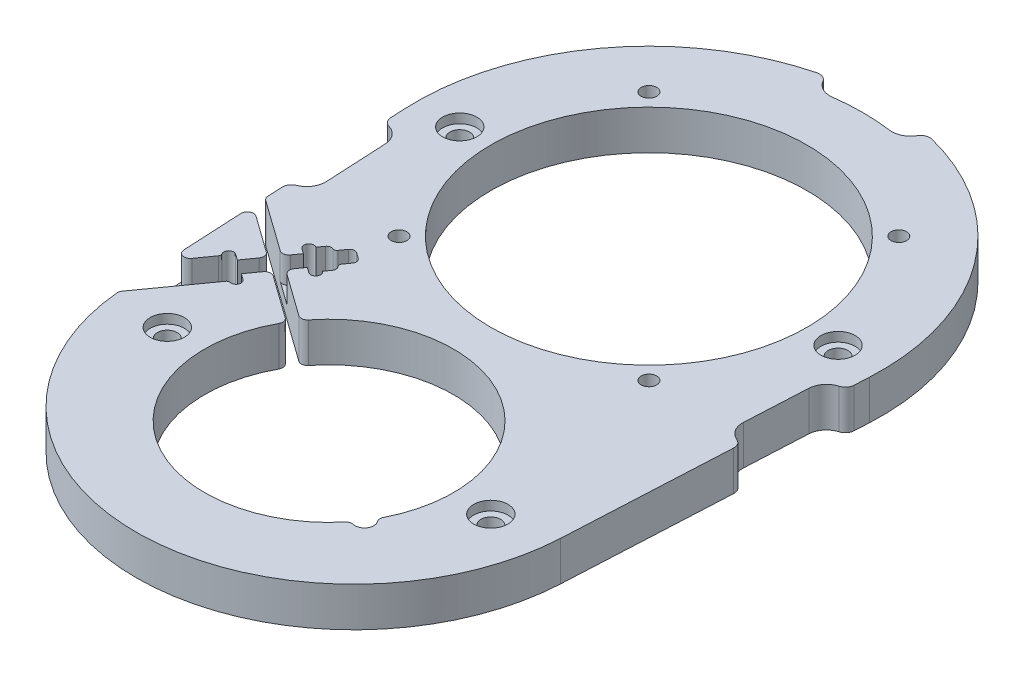
SolidWorks part; units mm, degrees
material "PC High Viscosity"
ref_plane "Front Plane" through (0, 0, 0) normal (0, 0, 1) x (1, 0, 0)
ref_plane "Top Plane" through (0, 0, 0) normal (0, 1, 0) x (1, 0, 0)
ref_plane "Right Plane" through (0, 0, 0) normal (1, 0, 0) x (0, 0, -1)
sketch "Sketch1" plane through (0, 0, 0) normal (0, 1, 0) x (1, 0, 0)
  line L0 (0, 0) -> (0, 102.8) construction
  line L1 (0, 0) -> (0, -40) construction
  line L2 (0, -40) -> (0, -52) construction
  line L3 (-74.7041, 99.0127) -> (-69.9102, 4.4557)
  line L4 (74.7041, 99.0127) -> (69.9102, 4.4557)
  line L5 (0, 102.8) -> (0, 165.6) construction
  line L6 (0, 102.8) -> (44.4063, 147.2063) construction
  line L7 (0, 102.8) -> (62.8, 102.8) construction
  line L8 (35.921, 138.721) -> (44.4063, 147.2063) construction
  line L10 (0, 102.8) -> (-74.8, 102.8) construction
  line L11 (0, 102.8) -> (0, 177.6) construction
  line L12 (0, 177.6) -> (-74.8, 177.6) construction
  line L13 (-74.8, 102.8) -> (-74.8, 177.6) construction
  line L14 (0, 0) -> (-74.8, 0) construction
  line L15 (0, 0) -> (0, -62) construction
  line L16 (0, -62) -> (-74.8, -62) construction
  line L17 (-74.8, 0) -> (-74.8, -62) construction
  circle A0 centre (0, 0) radius 40
  circle A1 centre (0, 102.8) radius 50.8
  circle A2 centre (0, 102.8) radius 62.8 construction
  circle A3 centre (0, 102.8) radius 74.8 construction
  circle A4 centre (0, 8) radius 60 construction
  circle A5 centre (0, 8) radius 70 construction
  arc A6 (-74.7041, 99.0127) -> (74.7041, 99.0127) centre (0, 102.8) cw
  arc A7 (-69.9102, 4.4557) -> (69.9102, 4.4557) centre (0, 8) ccw
  circle A8 centre (40.1637, 142.9637) radius 2.5
  circle A9 centre (40.1637, 62.6363) radius 2.5
  circle A10 centre (-40.1637, 62.6363) radius 2.5
  circle A11 centre (-40.1637, 142.9637) radius 2.5
  circle A12 centre (0, 102.8) radius 56.8 construction
  point P32 (0, 102.8)
  dimension "D1" = 80
  dimension "D2" = 101.6
  dimension "D4" = 12
  dimension "D3" = 12
  dimension "D5" = 10
  dimension "D6" = 120
  dimension "D7" = 12
  dimension "D9" = 5
  dimension "D8" = 45
  dimension "D11" = 239.6
  dimension "D12" = 149.6
  dimension "D10" = 4
extrude "Boss-Extrude1" add sketch "Sketch1" along normal blind 12.7
sketch "Sketch2" plane through (0, 0, 0) normal (0, -1, 0) x (1, 0, 0)
  line L0 (67.713, -99.3671) -> (62.9192, -4.8101)
  line L1 (-62.9192, -4.8101) -> (-67.713, -99.3671)
  line L2 (74.7041, -99.0127) -> (69.9102, -4.4557)
  line L3 (-69.9102, -4.4557) -> (-74.7041, -99.0127)
  line L4 (74.7041, -99.0127) -> (69.9102, -4.4557) construction
  line L5 (-69.9102, -4.4557) -> (-74.7041, -99.0127) construction
  line L6 (-57.1766, -5.1013) -> (-61.9704, -99.6582)
  line L7 (61.9704, -99.6582) -> (57.1766, -5.1013)
  arc A0 (62.9192, -4.8101) -> (-62.9192, -4.8101) centre (0, -8) ccw
  arc A1 (-67.713, -99.3671) -> (67.713, -99.3671) centre (0, -102.8) ccw
  arc A2 (-74.7041, -99.0127) -> (74.7041, -99.0127) centre (0, -102.8) ccw
  arc A3 (69.9102, -4.4557) -> (-69.9102, -4.4557) centre (0, -8) ccw
  arc A4 (-74.7041, -99.0127) -> (74.7041, -99.0127) centre (0, -102.8) ccw construction
  arc A5 (69.9102, -4.4557) -> (-69.9102, -4.4557) centre (0, -8) ccw construction
  arc A6 (57.1766, -5.1013) -> (-57.1766, -5.1013) centre (0, -8) ccw
  arc A7 (-61.9704, -99.6582) -> (61.9704, -99.6582) centre (0, -102.8) ccw
  dimension "D1" = 0
  dimension "D2" = 7
  dimension "D3" = 5.75
sketch "Sketch3" plane through (0, 12.7, 0) normal (0, 1, 0) x (1, 0, 0)
  line L0 (0, 0) -> (-72.3071, 51.7342)
  line L1 (-74.7041, 99.0127) -> (-69.9102, 4.4557) construction
  line L2 (0, 0) -> (0, 177.6) construction
  line L3 (-1.862, -2.6025) -> (-74.1692, 49.1317)
  line L4 (0, 0) -> (-1.862, -2.6025)
  line L5 (-72.3071, 51.7342) -> (-74.1692, 49.1317)
  arc A0 (74.7041, 99.0127) -> (-74.7041, 99.0127) centre (0, 102.8) ccw construction
  point P5 (-72.3071, 51.7342)
  dimension "D1" = 3.2
extrude "Cut-Extrude1" cut sketch "Sketch3" against normal through all
sketch "Sketch4" plane through (0, 12.7, 0) normal (0, 1, 0) x (1, 0, 0)
  line L0 (-53.1944, 34.1247) -> (-70.2088, 10.3444) construction
  line L1 (-72.1001, 47.6514) -> (-34.2887, 20.5981) construction
  line L2 (-72.1001, 47.6514) -> (-69.9102, 4.4557) construction
  line L3 (-55.4309, 35.7249) -> (-72.4453, 11.9446)
  line L4 (-50.9579, 32.5246) -> (-69.985, 5.9311)
  line L5 (-50.9579, 32.5246) -> (-67.9723, 8.7442) construction
  line L6 (-72.4453, 11.9446) -> (-69.985, 5.9311)
  line L7 (-55.4309, 35.7249) -> (-50.9579, 32.5246)
  dimension "D1" = 2.75
  dimension "D2" = 2.75
extrude "Cut-Extrude2" cut sketch "Sketch4" against normal blind 8.5
sketch "Sketch5" plane through (0, 12.7, 0) normal (0, 1, 0) x (1, 0, 0)
  line L0 (-55.4309, 35.7249) -> (-50.9579, 32.5246) construction
  line L1 (-53.1944, 34.1247) -> (-41.4405, 50.5529) construction
  line L2 (-32.531, 23.2752) -> (-72.3071, 51.7342) construction
  line L3 (-50.9579, 32.5246) -> (-39.204, 48.9527)
  line L4 (-55.4309, 35.7249) -> (-43.677, 52.1531)
  line L5 (-43.677, 52.1531) -> (-39.204, 48.9527)
  line L6 (-50.9579, 32.5246) -> (-55.4309, 35.7249)
  dimension "D1" = 17
  dimension "D2" = 2.75
  dimension "D3" = 2.75
extrude "Cut-Extrude3" cut sketch "Sketch5" against normal blind 8.5
sketch "Sketch6" plane through (0, 12.7, 0) normal (0, 1, 0) x (1, 0, 0)
  line L0 (-44.3499, 46.4865) -> (-57.2676, 28.4318) construction
  line L1 (-39.204, 48.9527) -> (-43.677, 52.1531) construction
  line L2 (-39.204, 48.9527) -> (-43.677, 52.1531) construction
  line L3 (-61.399, 31.3878) -> (-53.1362, 25.4759)
  line L4 (-53.1362, 25.4759) -> (-57.2093, 19.783) construction
  line L5 (-57.2093, 19.783) -> (-65.4722, 25.6949)
  line L6 (-65.4722, 25.6949) -> (-61.399, 31.3878) construction
  line L7 (-48.2536, 49.2795) -> (-40.4461, 43.6935)
  line L8 (-40.4461, 43.6935) -> (-44.5193, 38.0006) construction
  line L9 (-44.5193, 38.0006) -> (-52.3267, 43.5866)
  line L10 (-52.3267, 43.5866) -> (-48.2536, 49.2795) construction
  line L11 (-40.4461, 43.6935) -> (-42.6573, 40.6031)
  line L12 (-48.2536, 49.2795) -> (-50.4647, 46.1891)
  line L13 (-54.9982, 22.8734) -> (-57.2093, 19.783)
  line L14 (-63.2611, 28.7853) -> (-65.4722, 25.6949)
  line L15 (-50.9579, 32.5246) -> (-55.4309, 35.7249) construction
  line L16 (-49.0959, 35.1271) -> (-53.5689, 38.3274) construction
  arc A0 (-44.5193, 38.0006) -> (-42.6573, 40.6031) centre (-43.5883, 39.3018) ccw
  arc A1 (-52.3267, 43.5866) -> (-50.4647, 46.1891) centre (-51.3957, 44.8879) cw
  arc A2 (-54.9982, 22.8734) -> (-53.1362, 25.4759) centre (-54.0672, 24.1746) ccw
  arc A3 (-63.2611, 28.7853) -> (-61.399, 31.3878) centre (-62.33, 30.0865) cw
  point P4 (-41.4405, 50.5529)
  point P10 (-57.2676, 28.4318)
  point P15 (-44.3499, 46.4865)
  dimension "D6" = 3.2
  dimension "D7" = 3.2
  dimension "D1" = 7
  dimension "D2" = 7
  dimension "D3" = 9.6
  dimension "D4" = 10.16
  dimension "D5" = 7
  dimension "D8" = 5
extrude "Cut-Extrude4" cut sketch "Sketch6" against normal through all
sketch "Sketch7" plane through (0, 12.7, 0) normal (0, 1, 0) x (1, 0, 0)
  line L0 (-57.2093, 19.783) -> (-69.7624, 2.2379)
  line L2 (-65.4722, 25.6949) -> (-70.6221, 18.497)
  line L3 (-72.1001, 47.6514) -> (-70.4325, 14.7577) construction
  line L5 (-70.6221, 18.497) -> (-73.2088, 10.1923)
  line L6 (-73.2088, 10.1923) -> (-69.7624, 2.2379)
  line L7 (-70.2088, 10.3444) -> (-73.2088, 10.1923) construction
  line L8 (-69.985, 5.9311) -> (-70.4325, 14.7577) construction
  line L9 (-65.4722, 25.6949) -> (-57.2093, 19.783)
  line L10 (-59.1043, 21.1387) -> (-63.5773, 24.3391) construction
  line L11 (-63.2611, 28.7853) -> (-65.4722, 25.6949) construction
  line L12 (-57.2093, 19.783) -> (-54.9982, 22.8734) construction
  arc A0 (-69.9102, 4.4557) -> (69.9102, 4.4557) centre (0, 8) ccw construction
  dimension "D1" = 3
extrude "Cut-Extrude5" cut sketch "Sketch7" against normal up to surface (8.5 mm away) up to face at (-65.7748, 4.2, -16.5417)
fillet "Fillet1" radius 2 4 edges at (-72.1001, 6.35, -47.6514) (-72.3071, 6.35, -51.7342) (-34.2887, 6.35, -20.5981) (-32.531, 6.35, -23.2752)
fillet "Fillet2" radius 2 6 edges at (-69.7624, 8.45, -2.2379) (-70.6221, 8.45, -18.497) (-55.4309, 8.45, -35.7249) (-50.9579, 8.45, -32.5246) (-53.5689, 8.45, -38.3274) (-49.0959, 8.45, -35.1271)
fillet "Fillet3" radius 1.6 6 edges at (-48.2536, 6.35, -49.2795) (-40.4461, 6.35, -43.6935) (-57.2093, 2.1, -19.783) (-65.4722, 2.1, -25.6949) (-39.204, 8.45, -48.9527) (-43.677, 8.45, -52.1531)
fillet "Fillet4" radius 1 4 edges at (-54.9982, 6.35, -22.8734) (-63.2611, 6.35, -28.7853) (-42.1134, 8.45, -44.8864) (-46.5864, 8.45, -48.0867)
sketch "Sketch10" plane through (0, 12.7, 0) normal (0, 1, 0) x (1, 0, 0)
  line L0 (0, 0) -> (-52, 0) construction
  line L1 (0, 102.8) -> (-60.8, 102.8) construction
  line L2 (0, 102.8) -> (0, 0) construction
  circle A0 centre (0, 0) radius 52 construction
  arc A1 (-35.1624, 19.0685) -> (-31.3857, 24.7979) centre (0, 0) ccw construction
  circle A2 centre (-52, 0) radius 3.175
  circle A3 centre (0, 102.8) radius 60.8 construction
  circle A4 centre (0, 102.8) radius 50.8 construction
  circle A5 centre (-60.8, 102.8) radius 3.175
  circle A6 centre (60.8, 102.8) radius 3.175
  circle A7 centre (52, 0) radius 3.175
  dimension "D1" = 12
  dimension "D2" = 6.35
  dimension "D3" = 10
  dimension "D4" = 6.35
extrude "Cut-Extrude6" cut sketch "Sketch10" against normal through all
sketch "Sketch11" plane through (0, 12.7, 0) normal (0, 1, 0) x (1, 0, 0)
  line L0 (-33.3971, 22.0143) -> (33.3971, -22.0143) construction
  arc A0 (-35.1624, 19.0685) -> (-31.3857, 24.7979) centre (0, 0) ccw construction
  circle A1 centre (33.3971, -22.0143) radius 3
  point P9 (0, 0)
  dimension "D1" = 6
extrude "Cut-Extrude7" cut sketch "Sketch11" against normal through all
fillet "Fillet5" radius 2 2 edges at (31.6533, 6.35, 24.4554) (34.9531, 6.35, 19.4494)
sketch "Sketch12" plane through (0, 12.7, 0) normal (0, 1, 0) x (1, 0, 0)
  circle A0 centre (-60.8, 102.8) radius 5.5
  circle A1 centre (60.8, 102.8) radius 5.5
  circle A2 centre (52, 0) radius 5.5
  circle A3 centre (-52, 0) radius 5.5
  dimension "D1" = 11
extrude "Cut-Extrude8" cut sketch "Sketch12" against normal blind 3
sketch "Sketch13" plane through (0, 12.7, 0) normal (0, 1, 0) x (1, 0, 0)
  line L0 (0, 0) -> (0, 102.8) construction
  line L1 (-73.53, 75.8553) -> (-67.2101, 74.812) construction
  line L2 (-74.7041, 99.0127) -> (-72.356, 52.6979) construction
  line L3 (-73.0237, 65.8681) -> (-74.0364, 85.8425) construction
  line L4 (-67.0314, 66.1719) -> (-68.0441, 86.1463)
  line L5 (-79.016, 65.5643) -> (-80.0287, 85.5387)
  line L6 (67.0314, 66.1719) -> (68.0441, 86.1463)
  line L7 (79.016, 65.5643) -> (80.0287, 85.5387)
  line L8 (0, 102.8) -> (0, 177.6) construction
  arc A0 (-67.0314, 66.1719) -> (-79.016, 65.5643) centre (-73.0237, 65.8681) cw
  arc A1 (-68.0441, 86.1463) -> (-80.0287, 85.5387) centre (-74.0364, 85.8425) ccw
  arc A2 (67.0314, 66.1719) -> (79.016, 65.5643) centre (73.0237, 65.8681) ccw
  arc A3 (68.0441, 86.1463) -> (80.0287, 85.5387) centre (74.0364, 85.8425) cw
  arc A5 (9.9776, 176.9316) -> (-9.9776, 176.9316) centre (0, 102.8) ccw construction
  arc A6 (74.7041, 99.0127) -> (-74.7041, 99.0127) centre (0, 102.8) ccw construction
  arc A7 (10.778, 182.8779) -> (-10.778, 182.8779) centre (0, 102.8) ccw
  arc A8 (9.1773, 170.9852) -> (-9.1773, 170.9852) centre (0, 102.8) ccw
  arc A9 (10.778, 182.8779) -> (9.1773, 170.9852) centre (9.9776, 176.9316) cw
  arc A10 (-10.778, 182.8779) -> (-9.1773, 170.9852) centre (-9.9776, 176.9316) ccw
  point P11 (-73.53, 75.8553)
  point P23 (0, 177.6)
  dimension "D4" = 10
  dimension "D1" = 20
  dimension "D2" = 6
  dimension "D3" = 6
  dimension "D5" = 6
  dimension "D6" = 6
extrude "Cut-Extrude9" cut sketch "Sketch13" against normal through all
fillet "Fillet6" radius 3 6 edges at (72.7199, 6.35, -59.8758) (74.3402, 6.35, -91.8348) (-72.7199, 6.35, -59.8758) (-74.3402, 6.35, -91.8348) (15.8871, 6.35, -175.8934) (-15.8871, 6.35, -175.8934)
